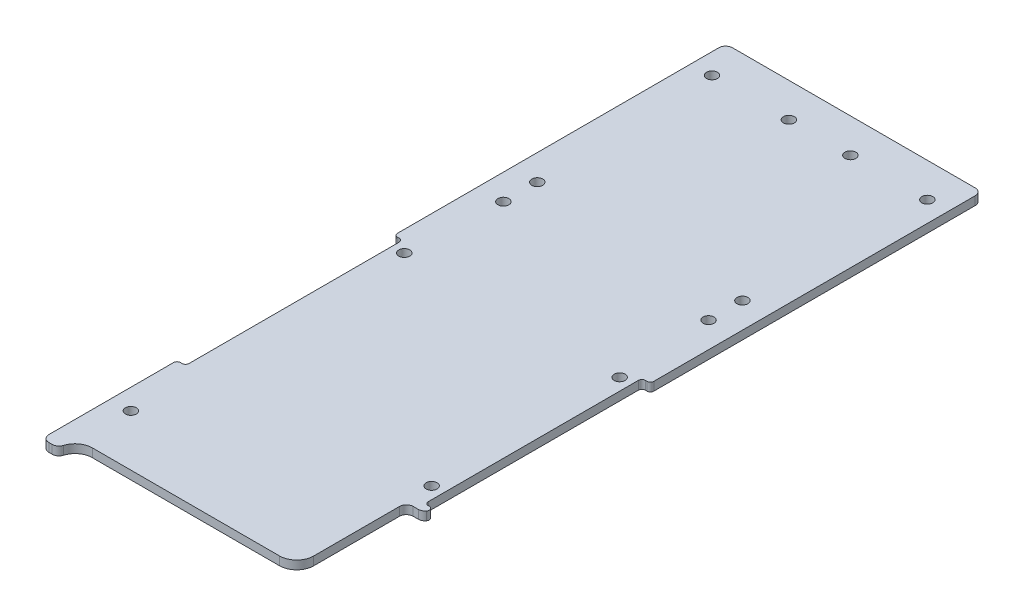
SolidWorks part; units mm, degrees
ref_plane "Front Plane" through (0, 0, 0) normal (0, 0, 1) x (1, 0, 0)
ref_plane "Top Plane" through (0, 0, 0) normal (0, 1, 0) x (1, 0, 0)
ref_plane "Right Plane" through (0, 0, 0) normal (1, 0, 0) x (0, 0, -1)
sketch "Sketch1" plane through (0, 0, 0) normal (0, 1, 0) x (1, 0, 0)
  line L0 (-39.9997, 0) -> (-39.9997, 114.3) construction
  line L1 (-47.625, 127) -> (47.625, 127)
  line L2 (-47.625, 127) -> (-47.625, -127)
  line L3 (-47.625, -127) -> (47.625, -127)
  line L4 (47.625, 127) -> (47.625, -127)
  line L5 (-47.625, 127) -> (47.625, -127) construction
  line L6 (-47.625, -127) -> (47.625, 127) construction
  line L7 (0, 0) -> (0, 127) construction
  line L8 (-39.9997, 0) -> (-39.9997, -101.6) construction
  line L9 (-39.9997, 0) -> (0, 0) construction
  line L10 (-41.275, -127) -> (-41.275, -120.65)
  line L11 (-41.275, -120.65) -> (41.275, -120.65)
  line L12 (41.275, -120.65) -> (41.275, -127)
  line L13 (-39.9997, 114.3) -> (-11.4247, 114.3) construction
  line L14 (39.9997, 114.3) -> (11.4247, 114.3) construction
  circle A0 centre (-39.9997, 114.3) radius 2.032
  circle A1 centre (-39.9997, 0) radius 2.032
  circle A2 centre (-39.9997, -101.6) radius 2.032
  circle A3 centre (39.9997, -101.6) radius 2.032
  circle A4 centre (39.9997, 0) radius 2.032
  circle A5 centre (39.9997, 114.3) radius 2.032
  circle A6 centre (-11.4247, 114.3) radius 2.032
  circle A7 centre (11.4247, 114.3) radius 2.032
  circle A8 centre (-39.9997, -69.85) radius 2.032
  circle A9 centre (39.9997, -69.85) radius 2.032
  point P0 (0, 0)
  dimension "D4" = 4.064
  dimension "D10" = 28.575
  dimension "D1" = 95.25
  dimension "D2" = 254
  dimension "D3" = 7.6253
  dimension "D5" = 12.7
  dimension "D6" = 25.4
  dimension "D7" = 6.35
  dimension "D8" = 6.35
  dimension "D9" = 6.35
  dimension "D11" = 69.85
extrude "Boss-Extrude1" add sketch "Sketch1" along normal blind 3.175 contours L4 L1 L2 L3 A4 A0 A1 A2 A3 A5 | A8 | A3 region at (0, 0, -2.6944) region at (39.9997, 0, 101.6) region at (-39.9997, 0, 69.85)
fillet "Fillet1" radius 2.54 4 edges at (-47.625, 1.5875, -127) (47.625, 1.5875, -127) (47.625, 1.5875, 127) (-47.625, 1.5875, 127)
fillet "Fillet2" radius 2.54 2 edges at (41.275, 1.5875, 127) (-41.275, 1.5875, 127)
fillet "Fillet3" radius 6.35 2 edges at (41.275, 1.5875, 120.65) (-41.275, 1.5875, 120.65)
sketch "Sketch2" plane through (0, 0, 0) normal (0, -1, 0) x (1, 0, 0)
  line L1 (43.815, 127) -> (45.085, 127) construction
  line L2 (40.6451, 123.5787) -> (40.6451, 79.8881)
  line L3 (40.6451, 79.8881) -> (47.625, 79.8881)
  line L11 (47.625, -124.46) -> (47.625, 124.46) construction
  line L12 (43.815, 127) -> (45.085, 127)
  line L13 (47.625, 79.8881) -> (47.625, 124.46)
  arc A0 (35.2956, 120.65) -> (41.3809, 125.1857) centre (35.2956, 127) ccw construction
  arc A1 (43.815, 127) -> (41.3809, 125.1857) centre (43.815, 124.46) ccw construction
  arc A2 (47.625, 124.46) -> (45.085, 127) centre (45.085, 124.46) ccw construction
  arc A3 (40.6451, 123.5787) -> (41.3809, 125.1857) centre (35.2956, 127) ccw
  arc A4 (43.815, 127) -> (41.3809, 125.1857) centre (43.815, 124.46) ccw
  arc A5 (47.625, 124.46) -> (45.085, 127) centre (45.085, 124.46) ccw
  dimension "D2" = 47.1119
  dimension "D1" = 6.9799
extrude "Cut-Extrude1" cut sketch "Sketch2" against normal through all
fillet "Fillet4" radius 6.35 1 edges at (40.6451, 1.5875, 123.5787)
fillet "Fillet5" radius 2.54 2 edges at (47.625, 1.5875, 79.8881) (40.6451, 1.5875, 79.8881)
sketch "Sketch3" plane through (0, 0, 0) normal (0, -1, 0) x (1, 0, 0)
  line L0 (-36.302, -49.7791) -> (-39.9088, -49.7791) construction
  line L1 (-40.4168, -49.276) -> (-40.4168, -45.7043) construction
  line L2 (-35.794, -45.7043) -> (-35.794, -49.276) construction
  line L3 (-39.9088, -45.2013) -> (-36.302, -45.2013) construction
  line L4 (-36.302, -37.2027) -> (-39.9088, -37.2027) construction
  line L5 (-35.794, -33.1279) -> (-35.794, -36.6996) construction
  line L6 (-40.4168, -36.6996) -> (-40.4168, -33.1279) construction
  line L7 (-39.9088, -32.6249) -> (-36.302, -32.6249) construction
  line L8 (36.2912, -32.6249) -> (39.898, -32.6249) construction
  line L9 (40.406, -33.1279) -> (40.406, -36.6996) construction
  line L10 (39.898, -37.2027) -> (36.2912, -37.2027) construction
  line L11 (35.7832, -36.6996) -> (35.7832, -33.1279) construction
  line L12 (36.2912, -45.2013) -> (39.898, -45.2013) construction
  line L13 (35.7832, -49.276) -> (35.7832, -45.7043) construction
  line L14 (40.406, -45.7043) -> (40.406, -49.276) construction
  line L15 (39.898, -49.7791) -> (36.2912, -49.7791) construction
  line L16 (-36.302, -49.7791) -> (-39.9088, -49.7791)
  line L17 (-40.4168, -49.276) -> (-40.4168, -45.7043)
  line L18 (-35.794, -45.7043) -> (-35.794, -49.276)
  line L19 (-39.9088, -45.2013) -> (-36.302, -45.2013)
  line L20 (-36.302, -37.2027) -> (-39.9088, -37.2027)
  line L21 (-35.794, -33.1279) -> (-35.794, -36.6996)
  line L22 (-40.4168, -36.6996) -> (-40.4168, -33.1279)
  line L23 (-39.9088, -32.6249) -> (-36.302, -32.6249)
  line L24 (36.2912, -32.6249) -> (39.898, -32.6249)
  line L25 (40.406, -33.1279) -> (40.406, -36.6996)
  line L26 (39.898, -37.2027) -> (36.2912, -37.2027)
  line L27 (35.7832, -36.6996) -> (35.7832, -33.1279)
  line L28 (36.2912, -45.2013) -> (39.898, -45.2013)
  line L29 (35.7832, -49.276) -> (35.7832, -45.7043)
  line L30 (40.406, -45.7043) -> (40.406, -49.276)
  line L31 (39.898, -49.7791) -> (36.2912, -49.7791)
  line L32 (-47.625, -25.836) -> (47.625, -25.836)
  line L33 (-47.625, -124.46) -> (-47.625, 124.46) construction
  line L34 (47.625, -124.46) -> (47.625, 77.3481) construction
  line L35 (0, -25.836) -> (0, -56.0686) construction
  line L1362 (-40.4168, -34.9138) -> (-35.794, -34.9138)
  line L1857 (-38.1054, -32.6249) -> (-38.1054, -37.2027)
  line L1858 (-38.1054, -45.2013) -> (-38.1054, -49.7791)
  line L1859 (-40.4168, -47.4902) -> (-35.794, -47.4902)
  circle A0 centre (-38.1054, -34.9138) radius 2.032
  circle A1 centre (-38.1054, -47.4902) radius 2.032
  circle A2 centre (38.1054, -47.4902) radius 2.032
  circle A3 centre (38.1054, -34.9138) radius 2.032
  ellipse E0 centre (-39.9088, -45.7043) end of major axis (-39.4008, -45.7043) minor radius 0.5031 (-39.9088, -45.2013) -> (-40.4168, -45.7043) ccw construction
  ellipse E1 centre (-39.9088, -49.276) end of major axis (-39.4008, -49.276) minor radius 0.5031 (-40.4168, -49.276) -> (-39.9088, -49.7791) ccw construction
  ellipse E6 centre (-36.302, -49.276) end of major axis (-35.794, -49.276) minor radius 0.5031 (-36.302, -49.7791) -> (-35.794, -49.276) ccw construction
  ellipse E7 centre (-36.302, -45.7043) end of major axis (-35.794, -45.7043) minor radius 0.5031 (-35.794, -45.7043) -> (-36.302, -45.2013) ccw construction
  ellipse E8 centre (-39.9088, -36.6996) end of major axis (-39.4008, -36.6996) minor radius 0.5031 (-40.4168, -36.6996) -> (-39.9088, -37.2027) ccw construction
  ellipse E9 centre (-36.302, -36.6996) end of major axis (-35.794, -36.6996) minor radius 0.5031 (-36.302, -37.2027) -> (-35.794, -36.6996) ccw construction
  ellipse E10 centre (-36.302, -33.1279) end of major axis (-35.794, -33.1279) minor radius 0.5031 (-35.794, -33.1279) -> (-36.302, -32.6249) ccw construction
  ellipse E11 centre (-39.9088, -33.1279) end of major axis (-39.4008, -33.1279) minor radius 0.5031 (-39.9088, -32.6249) -> (-40.4168, -33.1279) ccw construction
  ellipse E12 centre (39.898, -33.1279) end of major axis (40.406, -33.1279) minor radius 0.5031 (40.406, -33.1279) -> (39.898, -32.6249) ccw construction
  ellipse E13 centre (36.2912, -33.1279) end of major axis (36.7992, -33.1279) minor radius 0.5031 (36.2912, -32.6249) -> (35.7832, -33.1279) ccw construction
  ellipse E14 centre (39.898, -36.6996) end of major axis (40.406, -36.6996) minor radius 0.5031 (39.898, -37.2027) -> (40.406, -36.6996) ccw construction
  ellipse E15 centre (36.2912, -36.6996) end of major axis (36.7992, -36.6996) minor radius 0.5031 (35.7832, -36.6996) -> (36.2912, -37.2027) ccw construction
  ellipse E16 centre (36.2912, -45.7043) end of major axis (36.7992, -45.7043) minor radius 0.5031 (36.2912, -45.2013) -> (35.7832, -45.7043) ccw construction
  ellipse E17 centre (36.2912, -49.276) end of major axis (36.7992, -49.276) minor radius 0.5031 (35.7832, -49.276) -> (36.2912, -49.7791) ccw construction
  ellipse E18 centre (39.898, -45.7043) end of major axis (40.406, -45.7043) minor radius 0.5031 (40.406, -45.7043) -> (39.898, -45.2013) ccw construction
  ellipse E19 centre (39.898, -49.276) end of major axis (40.406, -49.276) minor radius 0.5031 (39.898, -49.7791) -> (40.406, -49.276) ccw construction
  ellipse E20 centre (-39.9088, -45.7043) end of major axis (-39.4008, -45.7043) minor radius 0.5031 (-39.9088, -45.2013) -> (-40.4168, -45.7043) ccw
  ellipse E21 centre (-39.9088, -49.276) end of major axis (-39.4008, -49.276) minor radius 0.5031 (-40.4168, -49.276) -> (-39.9088, -49.7791) ccw
  ellipse E22 centre (-36.302, -49.276) end of major axis (-35.794, -49.276) minor radius 0.5031 (-36.302, -49.7791) -> (-35.794, -49.276) ccw
  ellipse E23 centre (-36.302, -45.7043) end of major axis (-35.794, -45.7043) minor radius 0.5031 (-35.794, -45.7043) -> (-36.302, -45.2013) ccw
  ellipse E24 centre (-39.9088, -36.6996) end of major axis (-39.4008, -36.6996) minor radius 0.5031 (-40.4168, -36.6996) -> (-39.9088, -37.2027) ccw
  ellipse E25 centre (-36.302, -36.6996) end of major axis (-35.794, -36.6996) minor radius 0.5031 (-36.302, -37.2027) -> (-35.794, -36.6996) ccw
  ellipse E26 centre (-36.302, -33.1279) end of major axis (-35.794, -33.1279) minor radius 0.5031 (-35.794, -33.1279) -> (-36.302, -32.6249) ccw
  ellipse E27 centre (-39.9088, -33.1279) end of major axis (-39.4008, -33.1279) minor radius 0.5031 (-39.9088, -32.6249) -> (-40.4168, -33.1279) ccw
  ellipse E28 centre (39.898, -33.1279) end of major axis (40.406, -33.1279) minor radius 0.5031 (40.406, -33.1279) -> (39.898, -32.6249) ccw
  ellipse E29 centre (36.2912, -33.1279) end of major axis (36.7992, -33.1279) minor radius 0.5031 (36.2912, -32.6249) -> (35.7832, -33.1279) ccw
  ellipse E30 centre (39.898, -36.6996) end of major axis (40.406, -36.6996) minor radius 0.5031 (39.898, -37.2027) -> (40.406, -36.6996) ccw
  ellipse E31 centre (36.2912, -36.6996) end of major axis (36.7992, -36.6996) minor radius 0.5031 (35.7832, -36.6996) -> (36.2912, -37.2027) ccw
  ellipse E32 centre (36.2912, -45.7043) end of major axis (36.7992, -45.7043) minor radius 0.5031 (36.2912, -45.2013) -> (35.7832, -45.7043) ccw
  ellipse E33 centre (36.2912, -49.276) end of major axis (36.7992, -49.276) minor radius 0.5031 (35.7832, -49.276) -> (36.2912, -49.7791) ccw
  ellipse E34 centre (39.898, -45.7043) end of major axis (40.406, -45.7043) minor radius 0.5031 (40.406, -45.7043) -> (39.898, -45.2013) ccw
  ellipse E35 centre (39.898, -49.276) end of major axis (40.406, -49.276) minor radius 0.5031 (39.898, -49.7791) -> (40.406, -49.276) ccw
  dimension "D2" = 4.064
extrude "Cut-Extrude2" cut sketch "Sketch3" against normal through all contours A0 | A1 | A2 | A3
sketch "Sketch4" plane through (0, 3.175, 0) normal (0, 1, 0) x (1, 0, 0)
  line L11 (-47.625, 124.46) -> (-47.625, -124.46) construction
  line L12 (-47.625, -76.835) -> (-44.45, -76.835)
  line L13 (-47.625, -76.835) -> (-47.625, 3.81)
  line L15 (-47.625, 3.81) -> (-44.45, 3.81)
  line L16 (-44.45, -76.835) -> (-44.45, 3.81)
  line L17 (47.625, 124.46) -> (47.625, -77.3481) construction
  line L18 (47.625, -76.835) -> (44.45, -76.835)
  line L19 (47.625, -76.835) -> (47.625, 3.81)
  line L20 (47.625, 3.81) -> (44.45, 3.81)
  line L45 (44.45, -76.835) -> (44.45, 3.81)
  line L47 (43.1851, -79.8881) -> (45.085, -79.8881) construction
  dimension "D1" = 3.175
  dimension "D2" = 80.645
  dimension "D3" = 3.0531
extrude "Cut-Extrude3" cut sketch "Sketch4" against normal through all and the other way through all
fillet "Fillet6" radius 1.27 8 edges at (-44.45, 1.5875, -3.81) (-47.625, 1.5875, -3.81) (-47.625, 1.5875, 76.835) (-44.45, 1.5875, 76.835) (44.45, 1.5875, 76.835) (47.625, 1.5875, 76.835) (44.45, 1.5875, -3.81) (47.625, 1.5875, -3.81)
